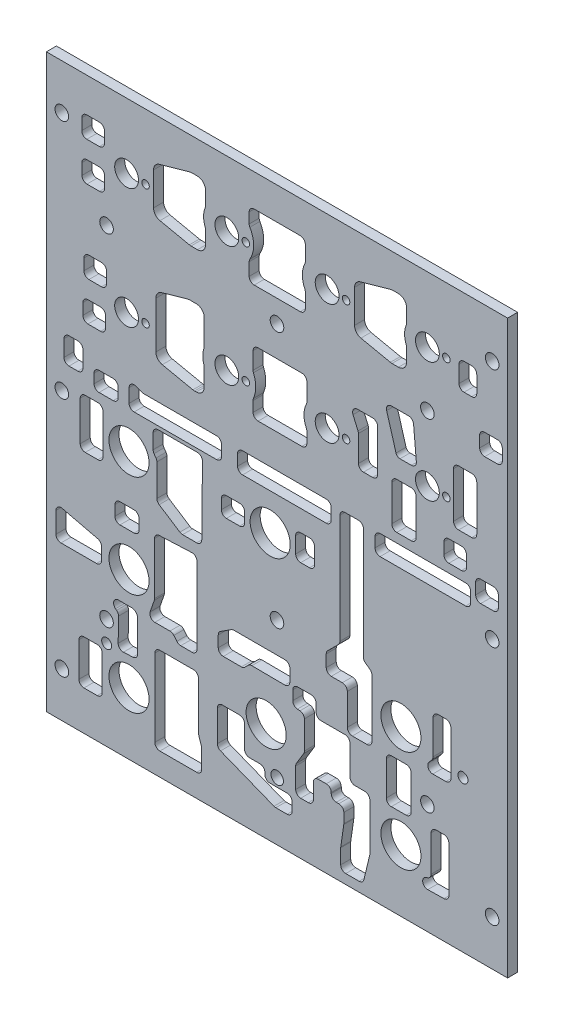
SolidWorks part; units mm, degrees
ref_plane "Front Plane" through (0, 0, 0) normal (0, 0, 1) x (1, 0, 0)
ref_plane "Top Plane" through (0, 0, 0) normal (0, 1, 0) x (1, 0, 0)
ref_plane "Right Plane" through (0, 0, 0) normal (1, 0, 0) x (0, 0, -1)
sketch "Sketch1" plane through (0, 0, 0) normal (0, 0, 1) x (1, 0, 0)
  line L4 (0, 180.975) -> (-146.05, 180.975)
  line L5 (-146.05, 180.975) -> (-146.05, 0)
  line L6 (-146.05, 0) -> (0, 0)
  line L7 (0, 0) -> (0, 180.975)
  line L8 (0, 180.975) -> (-146.05, 180.975)
  line L9 (-146.05, 180.975) -> (-146.05, 0)
  line L10 (-146.05, 0) -> (0, 0)
  line L11 (0, 0) -> (0, 180.975)
  dimension "D1" = 0
extrude "Boss-Extrude1" add sketch "Sketch1" against normal blind 3.175
hole_wizard "#6 Clearance Hole1" positions "Sketch3" profile "Sketch2" hole size "#6" standard "ANSI Inch" end condition through all
sketch "Sketch3" plane through (0, 0, -3.175) normal (0, 0, -1) x (-1, 0, 0)
  point P0 (25.4, 142.875)
  point P7 (73.025, 142.875)
  point P10 (127, 142.875)
  point P13 (25.4, 34.925)
  point P16 (73.025, 61.647)
  point P19 (127, 34.925)
  point P22 (4.8895, 14.2875)
  point P25 (141.1605, 14.2875)
  point P28 (4.8895, 90.4875)
  point P31 (141.1605, 90.4875)
  point P34 (141.1605, 166.6875)
  point P37 (4.8895, 166.6875)
sketch "Sketch2" plane through (-25.4, 142.875, -3.175) normal (1, 0, 0) x (0, 1, 0)
  line L0 (0, 0) -> (0, 3.175)
  line L1 (0, 3.175) -> (2.1526, 3.175)
  line L2 (2.1526, 3.175) -> (2.1526, 0)
  line L5 (2.1526, 0) -> (0, 0)
  line L11 (0, -6.35) -> (0, 107.95) construction
  dimension "Thru Hole Dia." = 4.3053
  dimension "Thru Hole Depth" = 3.175
hole_wizard "19/64 (0.29688) Diameter Hole1" positions "Sketch5" profile "Sketch4" hole size "19/64" standard "ANSI Inch" end condition through all
sketch "Sketch5" plane through (0, 0, -3.175) normal (0, 0, -1) x (-1, 0, 0)
  point P0 (25.4, 160.3248)
  point P3 (57.15, 160.3248)
  point P6 (88.9, 160.3248)
  point P9 (120.65, 160.3248)
  point P12 (25.4, 122.2248)
  point P15 (57.15, 122.2248)
  point P18 (88.9, 122.2248)
  point P21 (120.65, 122.2248)
sketch "Sketch4" plane through (-25.4, 160.3248, -3.175) normal (1, 0, 0) x (0, 1, 0)
  line L0 (0, 0) -> (0, 3.175)
  line L1 (0, 3.175) -> (3.7704, 3.175)
  line L2 (3.7704, 3.175) -> (3.7704, 0)
  line L5 (3.7704, 0) -> (0, 0)
  line L11 (0, -6.35) -> (0, 107.95) construction
  dimension "Thru Hole Dia." = 7.5408
  dimension "Thru Hole Depth" = 3.175
hole_wizard "1/2 (0.5) Diameter Hole1" positions "Sketch7" profile "Sketch6" hole size "1/2" standard "ANSI Inch" end condition through all
sketch "Sketch7" plane through (0, 0, -3.175) normal (0, 0, -1) x (-1, 0, 0)
  point P0 (75.184, 84.455)
  point P3 (119.888, 84.455)
  point P6 (119.888, 52.07)
  point P9 (33.782, 52.07)
  point P12 (33.782, 19.685)
  point P15 (119.888, 19.685)
  point P18 (76.454, 31.496)
sketch "Sketch6" plane through (-75.184, 84.455, -3.175) normal (1, 0, 0) x (0, 1, 0)
  line L0 (0, 0) -> (0, 3.175)
  line L1 (0, 3.175) -> (6.35, 3.175)
  line L2 (6.35, 3.175) -> (6.35, 0)
  line L5 (6.35, 0) -> (0, 0)
  line L11 (0, -6.35) -> (0, 107.95) construction
  dimension "Thru Hole Dia." = 12.7
  dimension "Thru Hole Depth" = 3.175
hole_wizard "5/32 (0.15625) Diameter Hole1" positions "Sketch9" profile "Sketch8" hole size "5/32" standard "ANSI Inch" end condition through all
sketch "Sketch9" plane through (0, 0, -3.175) normal (0, 0, -1) x (-1, 0, 0)
  point P0 (72.9632, 18.4682)
sketch "Sketch8" plane through (-72.9632, 18.4682, -3.175) normal (1, 0, 0) x (0, 1, 0)
  line L0 (0, 0) -> (0, 3.175)
  line L1 (0, 3.175) -> (1.9844, 3.175)
  line L2 (1.9844, 3.175) -> (1.9844, 0)
  line L5 (1.9844, 0) -> (0, 0)
  line L11 (0, -6.35) -> (0, 107.95) construction
  dimension "Thru Hole Dia." = 3.9688
  dimension "Thru Hole Depth" = 3.175
hole_wizard "3/32 (0.09375) Diameter Hole1" positions "Sketch10" profile "Sketch11" hole size "3/32" standard "ANSI Inch" end condition through all
sketch "Sketch10" plane through (0, 0, -3.175) normal (0, 0, -1) x (-1, 0, 0)
  point P0 (19.4, 160.3248)
  point P2 (51.15, 160.3248)
  point P4 (82.9, 160.3248)
  point P6 (114.65, 160.3248)
  point P8 (114.65, 122.2248)
  point P10 (82.9, 122.2248)
  point P12 (51.15, 122.2248)
  point P14 (19.4, 122.2248)
sketch "Sketch11" plane through (-19.4, 160.3248, -3.175) normal (1, 0, 0) x (0, 1, 0)
  line L0 (0, 0) -> (0, 3.175)
  line L1 (0, 3.175) -> (1.1906, 3.175)
  line L2 (1.1906, 3.175) -> (1.1906, 0)
  line L5 (1.1906, 0) -> (0, 0)
  line L11 (0, -6.35) -> (0, 107.95) construction
  dimension "Thru Hole Dia." = 2.3812
  dimension "Thru Hole Depth" = 3.175
sketch "Sketch14" plane through (0, 0, -3.175) normal (0, 0, -1) x (-1, 0, 0)
  line L0 (9.7672, 160.6329) -> (9.7672, 155.3272)
  line L1 (11.3547, 153.7397) -> (13.8015, 153.7397)
  line L2 (15.389, 155.3272) -> (15.389, 160.6329)
  line L3 (13.8015, 162.2204) -> (11.3547, 162.2204)
  line L4 (34.5586, 170.4142) -> (36.4003, 170.4142)
  line L5 (37.0961, 170.317) -> (46.6191, 167.6046)
  line L6 (48.4633, 165.1617) -> (48.4633, 154.7406)
  line L7 (46.4489, 152.2556) -> (37.1235, 150.2836)
  line L8 (36.598, 150.2286) -> (34.5586, 150.2286)
  line L9 (32.0186, 152.7686) -> (32.0186, 156.9396)
  line L10 (32.0186, 163.6743) -> (32.0186, 167.8742)
  line L11 (98.2115, 170.808) -> (100.0532, 170.808)
  line L12 (100.749, 170.7109) -> (110.272, 167.9984)
  line L13 (112.1162, 165.5556) -> (112.1162, 155.1345)
  line L14 (110.1017, 152.6494) -> (100.7763, 150.6774)
  line L15 (100.2508, 150.6225) -> (98.2115, 150.6225)
  line L16 (95.6715, 153.1625) -> (95.6715, 157.3335)
  line L17 (95.6715, 164.0681) -> (95.6715, 168.268)
  line L18 (81.8281, 169.1678) -> (81.8281, 165.8804)
  line L19 (80.2406, 149.9091) -> (65.6522, 149.9091)
  line L20 (64.0647, 151.4966) -> (64.0647, 156.2088)
  line L21 (65.6522, 170.7553) -> (80.2406, 170.7553)
  line L22 (81.8281, 155.5212) -> (81.8281, 151.4966)
  line L23 (64.0647, 164.4051) -> (64.0647, 169.1678)
  line L24 (129.2512, 170.0673) -> (133.2539, 170.0673)
  line L25 (134.8414, 168.4798) -> (134.8414, 164.9772)
  line L26 (133.2539, 163.3897) -> (129.2512, 163.3897)
  line L27 (127.6637, 164.9772) -> (127.6637, 168.4798)
  line L28 (129.2048, 157.7974) -> (133.2075, 157.7974)
  line L29 (134.795, 156.2099) -> (134.795, 152.7072)
  line L30 (133.2075, 151.1197) -> (129.2048, 151.1197)
  line L31 (127.6173, 152.7072) -> (127.6173, 156.2099)
  line L38 (9.7672, 131.1028) -> (9.7672, 116.698)
  line L39 (3.2616, 146.0268) -> (7.2643, 146.0268)
  line L40 (8.8518, 144.4393) -> (8.8518, 140.9366)
  line L41 (7.2643, 139.3491) -> (3.2616, 139.3491)
  line L42 (1.6741, 140.9366) -> (1.6741, 144.4393)
  line L43 (31.3598, 138.4891) -> (36.773, 138.4891)
  line L44 (38.2969, 136.4568) -> (35.3321, 126.2979)
  line L45 (34.083, 125.3612) -> (30.4776, 125.3612)
  line L46 (28.8963, 127.0889) -> (29.7785, 137.0417)
  line L47 (11.3547, 115.1105) -> (15.5328, 115.1105)
  line L48 (17.1203, 116.698) -> (17.1203, 131.1028)
  line L49 (15.5328, 132.6903) -> (11.3547, 132.6903)
  line L50 (48.956, 130.0101) -> (47.363, 126.3421)
  line L51 (47.2316, 125.7097) -> (47.2316, 117.4914)
  line L52 (45.6441, 115.9039) -> (42.7293, 115.9039)
  line L53 (41.1418, 117.4914) -> (41.1418, 130.6425)
  line L54 (42.7293, 132.23) -> (47.4999, 132.23)
  line L55 (80.6037, 131.7198) -> (80.6037, 126.3538)
  line L56 (79.0162, 113.2168) -> (65.1559, 113.2168)
  line L57 (63.5684, 114.8043) -> (63.5684, 118.2429)
  line L58 (65.1559, 133.3073) -> (79.0162, 133.3073)
  line L59 (80.6037, 118.0601) -> (80.6037, 114.8043)
  line L60 (63.5684, 126.171) -> (63.5684, 131.7198)
  line L61 (98.5982, 135.6202) -> (100.6455, 135.6202)
  line L62 (101.3413, 135.523) -> (109.5302, 133.1906)
  line L63 (111.3744, 130.7477) -> (111.3744, 116.0074)
  line L64 (109.3599, 113.5224) -> (99.6649, 111.4722)
  line L65 (99.1394, 111.4172) -> (98.5982, 111.4172)
  line L66 (96.0582, 113.9572) -> (96.0582, 119.3928)
  line L67 (96.0582, 125.1954) -> (96.0582, 133.0802)
  line L68 (128.5836, 131.9356) -> (132.5863, 131.9356)
  line L69 (134.1738, 130.3481) -> (134.1738, 126.8454)
  line L70 (132.5863, 125.2579) -> (128.5836, 125.2579)
  line L71 (126.9961, 126.8454) -> (126.9961, 130.3481)
  line L72 (128.8955, 119.5754) -> (132.8982, 119.5754)
  line L73 (134.4857, 117.9879) -> (134.4857, 114.4852)
  line L74 (132.8982, 112.8977) -> (128.8955, 112.8977)
  line L75 (127.308, 114.4852) -> (127.308, 117.9879)
  line L80 (134.4857, 99.9647) -> (134.4857, 105.0965)
  line L81 (136.0732, 106.684) -> (138.8818, 106.684)
  line L82 (140.4693, 105.0965) -> (140.4693, 99.9647)
  line L83 (138.8818, 98.3772) -> (136.0732, 98.3772)
  line L84 (4.5173, 105.1016) -> (8.52, 105.1016)
  line L85 (10.1075, 103.5141) -> (10.1075, 100.0114)
  line L86 (8.52, 98.4239) -> (4.5173, 98.4239)
  line L87 (2.9298, 100.0114) -> (2.9298, 103.5141)
  line L88 (14.5909, 111.1372) -> (18.5937, 111.1372)
  line L89 (20.1812, 109.5497) -> (20.1812, 106.0471)
  line L90 (18.5937, 104.4596) -> (14.5909, 104.4596)
  line L91 (13.0034, 106.0471) -> (13.0034, 109.5497)
  line L92 (30.5353, 119.2048) -> (35.0928, 119.2048)
  line L93 (36.6803, 117.6173) -> (36.6803, 106.232)
  line L94 (35.0928, 104.6445) -> (30.5353, 104.6445)
  line L95 (28.9478, 106.232) -> (28.9478, 117.6173)
  line L96 (45.6441, 65.1535) -> (45.6441, 100.3349)
  line L97 (47.2316, 101.9224) -> (51.5303, 101.9224)
  line L98 (53.1178, 100.3349) -> (53.1178, 65.7835)
  line L100 (42.9626, 43.3689) -> (42.9626, 61.5953)
  line L101 (43.6218, 62.8831) -> (44.9849, 63.8657)
  line L102 (53.5828, 64.661) -> (56.969, 61.2747)
  line L103 (57.434, 60.1522) -> (57.434, 56.3979)
  line L104 (55.8465, 54.8104) -> (52.3434, 54.8104)
  line L105 (50.7559, 53.2229) -> (50.7559, 43.3689)
  line L106 (49.1684, 41.7814) -> (44.5501, 41.7814)
  line L107 (67.1117, 82.7287) -> (67.1117, 87.7639)
  line L108 (65.5242, 89.3514) -> (62.7089, 89.3514)
  line L109 (61.1214, 87.7639) -> (61.1214, 82.7287)
  line L110 (62.7089, 81.1412) -> (65.5242, 81.1412)
  line L111 (17.9628, 45.6888) -> (17.9628, 59.6872)
  line L112 (19.5503, 61.2747) -> (21.9934, 61.2747)
  line L113 (23.5809, 59.6872) -> (23.5809, 48.8911)
  line L114 (23.9452, 47.8792) -> (24.9202, 46.7007)
  line L115 (23.697, 44.1013) -> (19.5503, 44.1013)
  line L116 (25.4886, 14.7678) -> (25.6589, 14.7487)
  line L117 (24.2487, 16.3262) -> (24.2487, 27.6802)
  line L118 (22.6612, 29.2677) -> (20.1812, 29.2677)
  line L119 (18.5937, 27.6802) -> (18.5937, 13.2755)
  line L120 (20.1548, 11.6882) -> (25.2848, 11.603)
  line L121 (32.1228, 42.5427) -> (36.8165, 42.5427)
  line L122 (38.404, 40.9552) -> (38.404, 30.1729)
  line L123 (36.8165, 28.5854) -> (32.1228, 28.5854)
  line L124 (30.5353, 30.1729) -> (30.5353, 40.9552)
  line L131 (43.6218, 25.2523) -> (43.6218, 12.2392)
  line L132 (43.6651, 11.8711) -> (43.6953, 11.7446)
  line L133 (43.6953, 11.7446) -> (45.484, 4.241)
  line L134 (47.0282, 3.0216) -> (51.2631, 3.0216)
  line L135 (52.8506, 4.6091) -> (52.8506, 9.2853)
  line L136 (52.8343, 9.5123) -> (51.8747, 16.1533)
  line L137 (51.8584, 16.3803) -> (51.8584, 19.4808)
  line L138 (53.4459, 21.0683) -> (54.259, 21.0683)
  line L139 (55.8465, 22.6558) -> (55.8465, 22.9529)
  line L140 (57.434, 24.5404) -> (59.9239, 24.5404)
  line L142 (65.7683, 40.3849) -> (66.5835, 40.4562)
  line L143 (68.0326, 42.0377) -> (68.0326, 44.998)
  line L144 (66.4451, 46.5855) -> (62.2379, 46.5855)
  line L145 (60.6504, 44.998) -> (60.6504, 42.5992)
  line L146 (59.0629, 41.0117) -> (51.4951, 41.0117)
  line L147 (49.9076, 39.4242) -> (49.9076, 30.1729)
  line L148 (48.3201, 28.5854) -> (45.2093, 28.5854)
  line L149 (43.6218, 26.9979) -> (43.6218, 25.2523)
  line L150 (68.9553, 46.6546) -> (68.9553, 50.4494)
  line L151 (70.5428, 52.0369) -> (86.6326, 52.0369)
  line L152 (87.4873, 51.7871) -> (90.8944, 49.6101)
  line L153 (91.6271, 48.2724) -> (91.6271, 44.761)
  line L154 (90.0396, 43.1735) -> (84.3014, 43.1735)
  line L155 (83.1789, 43.6384) -> (82.1297, 44.6876)
  line L156 (80.9942, 45.1525) -> (70.5558, 45.0672)
  line L157 (67.1117, 24.5868) -> (67.1117, 18.1303)
  line L158 (65.5242, 16.5428) -> (63.0989, 16.5428)
  line L163 (61.5114, 18.1303) -> (61.5114, 22.9529)
  line L165 (66.8832, 25.4074) -> (64.5524, 29.2677)
  line L166 (64.3238, 30.0883) -> (64.3238, 38.9242)
  line L167 (91.9128, 18.299) -> (91.9128, 28.1134)
  line L168 (90.3253, 29.7009) -> (84.8895, 29.7009)
  line L169 (83.302, 28.1134) -> (83.302, 21.1236)
  line L170 (81.7145, 19.5361) -> (78.4438, 19.5361)
  line L171 (76.8563, 17.9486) -> (76.8563, 17.3807)
  line L172 (75.2688, 15.7932) -> (69.8184, 15.7932)
  line L173 (68.2309, 14.2057) -> (68.2309, 11.594)
  line L174 (69.8184, 10.0065) -> (73.3881, 10.0065)
  line L175 (73.9724, 10.1179) -> (90.9097, 16.8229)
  line L176 (84.8489, 87.7639) -> (89.0654, 87.7639)
  line L177 (90.6529, 86.1764) -> (90.6529, 83.1046)
  line L178 (89.0654, 81.5171) -> (84.8489, 81.5171)
  line L179 (83.2614, 83.1046) -> (83.2614, 86.1764)
  line L180 (129.7198, 92.9203) -> (133.7466, 92.9203)
  line L181 (135.3341, 91.3328) -> (135.3341, 78.857)
  line L182 (133.7466, 77.2695) -> (129.7198, 77.2695)
  line L183 (128.1323, 78.857) -> (128.1323, 91.3328)
  line L184 (143.02, 56.7173) -> (143.02, 50.184)
  line L185 (141.4325, 48.5965) -> (130.1711, 48.5965)
  line L186 (128.5836, 50.184) -> (128.5836, 54.036)
  line L187 (129.8034, 55.5803) -> (141.0648, 58.2616)
  line L188 (135.7336, 24.8954) -> (135.7336, 14.0589)
  line L189 (134.1461, 12.4714) -> (129.9507, 12.4714)
  line L190 (128.3632, 14.0589) -> (128.3632, 24.8954)
  line L191 (129.9507, 26.4829) -> (134.1461, 26.4829)
  line L192 (98.4374, 70.1232) -> (102.927, 70.1232)
  line L193 (103.7933, 70.3805) -> (110.3296, 74.6375)
  line L194 (111.0507, 75.9677) -> (111.0507, 86.0205)
  line L195 (111.3413, 86.936) -> (111.9636, 87.8177)
  line L196 (112.2542, 88.7332) -> (112.2542, 93.4348)
  line L197 (110.6667, 95.0223) -> (98.2147, 95.0223)
  line L198 (96.6273, 93.4186) -> (96.85, 71.6944)
  line L199 (13.2867, 101.7189) -> (40.3927, 101.7189)
  line L200 (41.9802, 100.1314) -> (41.9802, 96.9635)
  line L201 (40.3927, 95.376) -> (13.2867, 95.376)
  line L202 (11.6992, 96.9635) -> (11.6992, 100.1314)
  line L203 (83.9216, 102.6251) -> (57.434, 102.6251)
  line L204 (55.8465, 101.0376) -> (55.8465, 97.6017)
  line L205 (57.434, 96.0142) -> (83.9216, 96.0142)
  line L206 (85.5091, 97.6017) -> (85.5091, 101.0376)
  line L207 (92.1689, 102.6251) -> (115.232, 102.6251)
  line L208 (115.789, 102.726) -> (117.7111, 103.4462)
  line L209 (119.8556, 101.9596) -> (119.8556, 97.6777)
  line L210 (118.2681, 96.0902) -> (92.1689, 96.0902)
  line L211 (90.5814, 97.6777) -> (90.5814, 101.0376)
  line L212 (124.9027, 101.9596) -> (129.3791, 101.9596)
  line L213 (130.9666, 100.3721) -> (130.9666, 97.4731)
  line L214 (129.3791, 95.8856) -> (124.9027, 95.8856)
  line L215 (123.3152, 97.4731) -> (123.3152, 100.3721)
  line L216 (118.2868, 62.8831) -> (122.7428, 62.8831)
  line L217 (124.3303, 64.4706) -> (124.3303, 67.6675)
  line L218 (122.7428, 69.255) -> (118.2868, 69.255)
  line L219 (116.6993, 67.6675) -> (116.6993, 64.4706)
  line L220 (99.9975, 66.6672) -> (110.2768, 66.2149)
  line L221 (111.7946, 64.6289) -> (111.7946, 48.1514)
  line L222 (111.8816, 47.6331) -> (113.2086, 43.7913)
  line L223 (111.7081, 41.6855) -> (106.9185, 41.6855)
  line L224 (105.6937, 41.108) -> (104.7376, 39.9485)
  line L225 (103.5128, 39.371) -> (99.9277, 39.371)
  line L226 (98.3402, 40.9585) -> (98.3402, 65.0812)
  line L227 (123.3155, 30.1394) -> (123.1999, 37.6519)
  line L231 (117.1597, 40.098) -> (117.1597, 30.2424)
  line L232 (118.6794, 28.6564) -> (121.6604, 28.5289)
  line L235 (119.0974, 42.0356) -> (123.1757, 42.0356)
  line L236 (124.1569, 39.2002) -> (123.806, 38.9242)
  line L238 (99.477, 34.8237) -> (110.1206, 34.8237)
  line L239 (111.7081, 33.2362) -> (111.7081, 8.7739)
  line L240 (110.1206, 7.1864) -> (98.4375, 7.1864)
  line L241 (96.85, 8.7739) -> (96.85, 14.4973)
  line L242 (96.9277, 14.9877) -> (97.8118, 17.7095)
  line L243 (97.8895, 18.1999) -> (97.8895, 33.2362)
  arc A0 (13.8015, 153.7397) -> (15.389, 155.3272) centre (13.8015, 155.3272) ccw
  arc A1 (9.7672, 160.6329) -> (11.3547, 162.2204) centre (11.3547, 160.6329) cw
  arc A2 (15.389, 160.6329) -> (13.8015, 162.2204) centre (13.8015, 160.6329) ccw
  arc A3 (9.7672, 155.3272) -> (11.3547, 153.7397) centre (11.3547, 155.3272) ccw
  arc A4 (34.5586, 150.2286) -> (32.0186, 152.7686) centre (34.5586, 152.7686) cw
  arc A5 (37.1235, 150.2836) -> (36.598, 150.2286) centre (36.598, 152.7686) cw
  arc A6 (48.4633, 154.7406) -> (46.4489, 152.2556) centre (45.9233, 154.7406) cw
  arc A7 (46.6191, 167.6046) -> (48.4633, 165.1617) centre (45.9233, 165.1617) cw
  arc A8 (36.4003, 170.4142) -> (37.0961, 170.317) centre (36.4003, 167.8742) cw
  arc A9 (34.5586, 170.4142) -> (32.0186, 167.8742) centre (34.5586, 167.8742) ccw
  arc A10 (32.1741, 157.8147) -> (32.1741, 162.7992) centre (25.3826, 160.3069) ccw
  arc A11 (32.1741, 162.7992) -> (32.0186, 163.6743) centre (34.5586, 163.6743) cw
  arc A12 (32.1741, 157.8147) -> (32.0186, 156.9396) centre (34.5586, 156.9396) ccw
  arc A13 (98.2115, 150.6225) -> (95.6715, 153.1625) centre (98.2115, 153.1625) cw
  arc A14 (100.7763, 150.6774) -> (100.2508, 150.6225) centre (100.2508, 153.1625) cw
  arc A15 (112.1162, 155.1345) -> (110.1017, 152.6494) centre (109.5762, 155.1345) cw
  arc A16 (110.272, 167.9984) -> (112.1162, 165.5556) centre (109.5762, 165.5556) cw
  arc A17 (100.0532, 170.808) -> (100.749, 170.7109) centre (100.0532, 168.268) cw
  arc A18 (98.2115, 170.808) -> (95.6715, 168.268) centre (98.2115, 168.268) ccw
  arc A19 (95.8269, 158.2085) -> (95.8269, 163.1931) centre (89.0355, 160.7008) ccw
  arc A20 (95.8269, 163.1931) -> (95.6715, 164.0681) centre (98.2115, 164.0681) cw
  arc A21 (95.8269, 158.2085) -> (95.6715, 157.3335) centre (98.2115, 157.3335) ccw
  arc A22 (64.2216, 156.8969) -> (64.2216, 163.7169) centre (57.1326, 160.3069) ccw
  arc A23 (81.6085, 165.0748) -> (81.6085, 156.3268) centre (89.0355, 160.7008) ccw
  arc A24 (64.2216, 163.7169) -> (64.0647, 164.4051) centre (65.6522, 164.4051) cw
  arc A25 (64.2216, 156.8969) -> (64.0647, 156.2088) centre (65.6522, 156.2088) ccw
  arc A26 (81.6085, 156.3268) -> (81.8281, 155.5212) centre (80.2406, 155.5212) cw
  arc A27 (81.6085, 165.0748) -> (81.8281, 165.8804) centre (80.2406, 165.8804) ccw
  arc A28 (81.8281, 169.1678) -> (80.2406, 170.7553) centre (80.2406, 169.1678) ccw
  arc A29 (64.0647, 169.1678) -> (65.6522, 170.7553) centre (65.6522, 169.1678) cw
  arc A30 (65.6522, 149.9091) -> (64.0647, 151.4966) centre (65.6522, 151.4966) cw
  arc A31 (81.8281, 151.4966) -> (80.2406, 149.9091) centre (80.2406, 151.4966) cw
  arc A32 (129.2512, 170.0673) -> (127.6637, 168.4798) centre (129.2512, 168.4798) ccw
  arc A33 (129.2512, 163.3897) -> (127.6637, 164.9772) centre (129.2512, 164.9772) cw
  arc A34 (134.8414, 164.9772) -> (133.2539, 163.3897) centre (133.2539, 164.9772) cw
  arc A35 (133.2539, 170.0673) -> (134.8414, 168.4798) centre (133.2539, 168.4798) cw
  arc A36 (129.2048, 157.7974) -> (127.6173, 156.2099) centre (129.2048, 156.2099) ccw
  arc A37 (129.2048, 151.1197) -> (127.6173, 152.7072) centre (129.2048, 152.7072) cw
  arc A38 (134.795, 152.7072) -> (133.2075, 151.1197) centre (133.2075, 152.7072) cw
  arc A39 (133.2075, 157.7974) -> (134.795, 156.2099) centre (133.2075, 156.2099) cw
  arc A50 (29.7785, 137.0417) -> (31.3598, 138.4891) centre (31.3598, 136.9016) cw
  arc A51 (3.2616, 146.0268) -> (1.6741, 144.4393) centre (3.2616, 144.4393) ccw
  arc A52 (3.2616, 139.3491) -> (1.6741, 140.9366) centre (3.2616, 140.9366) cw
  arc A53 (8.8518, 140.9366) -> (7.2643, 139.3491) centre (7.2643, 140.9366) cw
  arc A54 (7.2643, 146.0268) -> (8.8518, 144.4393) centre (7.2643, 144.4393) cw
  arc A55 (128.5836, 131.9356) -> (126.9961, 130.3481) centre (128.5836, 130.3481) ccw
  arc A56 (36.773, 138.4891) -> (38.2969, 136.4568) centre (36.773, 136.9016) cw
  arc A57 (30.4776, 125.3612) -> (28.8963, 127.0889) centre (30.4776, 126.9487) cw
  arc A58 (35.3321, 126.2979) -> (34.083, 125.3612) centre (34.083, 126.6624) cw
  arc A60 (9.7672, 116.698) -> (11.3547, 115.1105) centre (11.3547, 116.698) ccw
  arc A61 (15.5328, 115.1105) -> (17.1203, 116.698) centre (15.5328, 116.698) ccw
  arc A62 (17.1203, 131.1028) -> (15.5328, 132.6903) centre (15.5328, 131.1028) ccw
  arc A63 (9.7672, 131.1028) -> (11.3547, 132.6903) centre (11.3547, 131.1028) cw
  arc A64 (42.7293, 115.9039) -> (41.1418, 117.4914) centre (42.7293, 117.4914) cw
  arc A65 (47.2316, 117.4914) -> (45.6441, 115.9039) centre (45.6441, 117.4914) cw
  arc A66 (47.363, 126.3421) -> (47.2316, 125.7097) centre (48.8191, 125.7097) ccw
  arc A67 (41.1418, 130.6425) -> (42.7293, 132.23) centre (42.7293, 130.6425) cw
  arc A68 (48.956, 130.0101) -> (47.4999, 132.23) centre (47.4999, 130.6425) ccw
  arc A69 (80.4797, 125.7387) -> (80.4797, 118.6752) centre (88.8826, 122.2069) ccw
  arc A70 (63.7326, 118.9461) -> (63.7326, 125.4678) centre (57.1326, 122.2069) ccw
  arc A71 (63.7326, 125.4678) -> (63.5684, 126.171) centre (65.1559, 126.171) cw
  arc A72 (63.7326, 118.9461) -> (63.5684, 118.2429) centre (65.1559, 118.2429) ccw
  arc A73 (65.1559, 113.2168) -> (63.5684, 114.8043) centre (65.1559, 114.8043) cw
  arc A74 (80.6037, 114.8043) -> (79.0162, 113.2168) centre (79.0162, 114.8043) cw
  arc A75 (80.4797, 118.6752) -> (80.6037, 118.0601) centre (79.0162, 118.0601) cw
  arc A76 (80.4797, 125.7387) -> (80.6037, 126.3538) centre (79.0162, 126.3538) ccw
  arc A77 (80.6037, 131.7198) -> (79.0162, 133.3073) centre (79.0162, 131.7198) ccw
  arc A78 (63.5684, 131.7198) -> (65.1559, 133.3073) centre (65.1559, 131.7198) cw
  arc A79 (98.5982, 111.4172) -> (96.0582, 113.9572) centre (98.5982, 113.9572) cw
  arc A80 (99.6649, 111.4722) -> (99.1394, 111.4172) centre (99.1394, 113.9572) cw
  arc A81 (111.3744, 116.0074) -> (109.3599, 113.5224) centre (108.8344, 116.0074) cw
  arc A82 (109.5302, 133.1906) -> (111.3744, 130.7477) centre (108.8344, 130.7477) cw
  arc A83 (100.6455, 135.6202) -> (101.3413, 135.523) centre (100.6455, 133.0802) cw
  arc A84 (98.5982, 135.6202) -> (96.0582, 133.0802) centre (98.5982, 133.0802) ccw
  arc A85 (96.1501, 119.9657) -> (96.1501, 124.6224) centre (89.0819, 122.2941) ccw
  arc A86 (96.1501, 124.6224) -> (96.0582, 125.1954) centre (97.8895, 125.1954) cw
  arc A87 (96.1501, 119.9657) -> (96.0582, 119.3928) centre (97.8895, 119.3928) ccw
  arc A88 (128.5836, 125.2579) -> (126.9961, 126.8454) centre (128.5836, 126.8454) cw
  arc A89 (134.1738, 126.8454) -> (132.5863, 125.2579) centre (132.5863, 126.8454) cw
  arc A90 (132.5863, 131.9356) -> (134.1738, 130.3481) centre (132.5863, 130.3481) cw
  arc A91 (128.8955, 119.5754) -> (127.308, 117.9879) centre (128.8955, 117.9879) ccw
  arc A92 (128.8955, 112.8977) -> (127.308, 114.4852) centre (128.8955, 114.4852) cw
  arc A93 (134.4857, 114.4852) -> (132.8982, 112.8977) centre (132.8982, 114.4852) cw
  arc A94 (132.8982, 119.5754) -> (134.4857, 117.9879) centre (132.8982, 117.9879) cw
  arc A99 (134.4857, 99.9647) -> (136.0732, 98.3772) centre (136.0732, 99.9647) ccw
  arc A100 (140.4693, 99.9647) -> (138.8818, 98.3772) centre (138.8818, 99.9647) cw
  arc A101 (138.8818, 106.684) -> (140.4693, 105.0965) centre (138.8818, 105.0965) cw
  arc A102 (134.4857, 105.0965) -> (136.0732, 106.684) centre (136.0732, 105.0965) cw
  arc A103 (4.5173, 105.1016) -> (2.9298, 103.5141) centre (4.5173, 103.5141) ccw
  arc A104 (4.5173, 98.4239) -> (2.9298, 100.0114) centre (4.5173, 100.0114) cw
  arc A105 (10.1075, 100.0114) -> (8.52, 98.4239) centre (8.52, 100.0114) cw
  arc A106 (8.52, 105.1016) -> (10.1075, 103.5141) centre (8.52, 103.5141) cw
  arc A107 (14.5909, 111.1372) -> (13.0034, 109.5497) centre (14.5909, 109.5497) ccw
  arc A108 (14.5909, 104.4596) -> (13.0034, 106.0471) centre (14.5909, 106.0471) cw
  arc A109 (20.1812, 106.0471) -> (18.5937, 104.4596) centre (18.5937, 106.0471) cw
  arc A110 (18.5937, 111.1372) -> (20.1812, 109.5497) centre (18.5937, 109.5497) cw
  arc A111 (30.5353, 119.2048) -> (28.9478, 117.6173) centre (30.5353, 117.6173) ccw
  arc A112 (30.5353, 104.6445) -> (28.9478, 106.232) centre (30.5353, 106.232) cw
  arc A113 (36.6803, 106.232) -> (35.0928, 104.6445) centre (35.0928, 106.232) cw
  arc A114 (35.0928, 119.2048) -> (36.6803, 117.6173) centre (35.0928, 117.6173) cw
  arc A115 (45.6441, 100.3349) -> (47.2316, 101.9224) centre (47.2316, 100.3349) cw
  arc A116 (51.5303, 101.9224) -> (53.1178, 100.3349) centre (51.5303, 100.3349) cw
  arc A119 (53.1178, 65.7835) -> (53.5828, 64.661) centre (54.7053, 65.7835) ccw
  arc A120 (56.969, 61.2747) -> (57.434, 60.1522) centre (55.8465, 60.1522) cw
  arc A121 (57.434, 56.3979) -> (55.8465, 54.8104) centre (55.8465, 56.3979) cw
  arc A122 (42.9626, 43.3689) -> (44.5501, 41.7814) centre (44.5501, 43.3689) ccw
  arc A123 (50.7559, 43.3689) -> (49.1684, 41.7814) centre (49.1684, 43.3689) cw
  arc A124 (52.3434, 54.8104) -> (50.7559, 53.2229) centre (52.3434, 53.2229) ccw
  arc A125 (42.9626, 61.5953) -> (43.6218, 62.8831) centre (44.5501, 61.5953) cw
  arc A126 (45.6441, 65.1535) -> (44.9849, 63.8657) centre (44.0566, 65.1535) cw
  arc A127 (61.1214, 82.7287) -> (62.7089, 81.1412) centre (62.7089, 82.7287) ccw
  arc A128 (62.7089, 89.3514) -> (61.1214, 87.7639) centre (62.7089, 87.7639) ccw
  arc A129 (67.1117, 87.7639) -> (65.5242, 89.3514) centre (65.5242, 87.7639) ccw
  arc A130 (67.1117, 82.7287) -> (65.5242, 81.1412) centre (65.5242, 82.7287) cw
  arc A131 (17.9628, 59.6872) -> (19.5503, 61.2747) centre (19.5503, 59.6872) cw
  arc A132 (21.9934, 61.2747) -> (23.5809, 59.6872) centre (21.9934, 59.6872) cw
  arc A133 (23.5809, 48.8911) -> (23.9452, 47.8792) centre (25.1684, 48.8911) ccw
  arc A134 (24.9202, 46.7007) -> (23.697, 44.1013) centre (23.697, 45.6888) cw
  arc A135 (17.9628, 45.6888) -> (19.5503, 44.1013) centre (19.5503, 45.6888) ccw
  circle A136 centre (14.1329, 47.8792) radius 1.5875
  arc A137 (20.1812, 29.2677) -> (18.5937, 27.6802) centre (20.1812, 27.6802) ccw
  arc A138 (24.2487, 27.6802) -> (22.6612, 29.2677) centre (22.6612, 27.6802) ccw
  arc A139 (18.5937, 13.2755) -> (20.1548, 11.6882) centre (20.1812, 13.2755) ccw
  arc A140 (25.4886, 14.7678) -> (25.2848, 11.603) centre (25.3112, 13.1902) cw
  arc A141 (25.6589, 14.7487) -> (24.2487, 16.3262) centre (25.8362, 16.3262) cw
  arc A142 (32.1228, 42.5427) -> (30.5353, 40.9552) centre (32.1228, 40.9552) ccw
  arc A143 (36.8165, 42.5427) -> (38.404, 40.9552) centre (36.8165, 40.9552) cw
  arc A144 (38.404, 30.1729) -> (36.8165, 28.5854) centre (36.8165, 30.1729) cw
  arc A145 (32.1228, 28.5854) -> (30.5353, 30.1729) centre (32.1228, 30.1729) cw
  arc A151 (43.6218, 12.2392) -> (43.6651, 11.8711) centre (45.2093, 12.2392) ccw
  arc A152 (45.2093, 28.5854) -> (43.6218, 26.9979) centre (45.2093, 26.9979) ccw
  arc A153 (49.9076, 30.1729) -> (48.3201, 28.5854) centre (48.3201, 30.1729) cw
  arc A154 (51.4951, 41.0117) -> (49.9076, 39.4242) centre (51.4951, 39.4242) ccw
  arc A155 (60.6504, 42.5992) -> (59.0629, 41.0117) centre (59.0629, 42.5992) cw
  arc A156 (62.2379, 46.5855) -> (60.6504, 44.998) centre (62.2379, 44.998) ccw
  arc A157 (68.0326, 44.998) -> (66.4451, 46.5855) centre (66.4451, 44.998) ccw
  arc A158 (66.5835, 40.4562) -> (68.0326, 42.0377) centre (66.4451, 42.0377) ccw
  arc A159 (64.3238, 38.9242) -> (65.7683, 40.3849) centre (65.9067, 38.8034) cw
  arc A161 (55.8465, 22.9529) -> (57.434, 24.5404) centre (57.434, 22.9529) cw
  arc A162 (51.8584, 19.4808) -> (53.4459, 21.0683) centre (53.4459, 19.4808) cw
  arc A163 (51.8747, 16.1533) -> (51.8584, 16.3803) centre (53.4459, 16.3803) cw
  arc A164 (52.8506, 9.2853) -> (52.8343, 9.5123) centre (51.2631, 9.2853) ccw
  arc A165 (51.2631, 3.0216) -> (52.8506, 4.6091) centre (51.2631, 4.6091) ccw
  arc A166 (45.484, 4.241) -> (47.0282, 3.0216) centre (47.0282, 4.6091) ccw
  arc A167 (54.259, 21.0683) -> (55.8465, 22.6558) centre (54.259, 22.6558) ccw
  arc A168 (82.1297, 44.6876) -> (80.9942, 45.1525) centre (81.0072, 43.5651) ccw
  arc A169 (84.3014, 43.1735) -> (83.1789, 43.6384) centre (84.3014, 44.761) cw
  arc A170 (91.6271, 44.761) -> (90.0396, 43.1735) centre (90.0396, 44.761) cw
  arc A171 (90.8944, 49.6101) -> (91.6271, 48.2724) centre (90.0396, 48.2724) cw
  arc A172 (86.6326, 52.0369) -> (87.4873, 51.7871) centre (86.6326, 50.4494) cw
  arc A173 (68.9553, 50.4494) -> (70.5428, 52.0369) centre (70.5428, 50.4494) cw
  arc A174 (68.9553, 46.6546) -> (70.5558, 45.0672) centre (70.5428, 46.6546) ccw
  arc A175 (67.1117, 18.1303) -> (65.5242, 16.5428) centre (65.5242, 18.1303) cw
  arc A176 (63.0989, 16.5428) -> (61.5114, 18.1303) centre (63.0989, 18.1303) cw
  arc A177 (61.5114, 22.9529) -> (59.9239, 24.5404) centre (59.9239, 22.9529) ccw
  arc A178 (67.1117, 24.5868) -> (66.8832, 25.4074) centre (65.5242, 24.5868) ccw
  arc A179 (64.5524, 29.2677) -> (64.3238, 30.0883) centre (65.9113, 30.0883) cw
  arc A180 (91.9128, 18.299) -> (90.9097, 16.8229) centre (90.3253, 18.299) cw
  arc A181 (91.9128, 28.1134) -> (90.3253, 29.7009) centre (90.3253, 28.1134) ccw
  arc A182 (84.8895, 29.7009) -> (83.302, 28.1134) centre (84.8895, 28.1134) ccw
  arc A183 (83.302, 21.1236) -> (81.7145, 19.5361) centre (81.7145, 21.1236) cw
  arc A184 (78.4438, 19.5361) -> (76.8563, 17.9486) centre (78.4438, 17.9486) ccw
  arc A185 (76.8563, 17.3807) -> (75.2688, 15.7932) centre (75.2688, 17.3807) cw
  arc A186 (69.8184, 15.7932) -> (68.2309, 14.2057) centre (69.8184, 14.2057) ccw
  arc A187 (68.2309, 11.594) -> (69.8184, 10.0065) centre (69.8184, 11.594) ccw
  arc A188 (73.3881, 10.0065) -> (73.9724, 10.1179) centre (73.3881, 11.594) ccw
  arc A189 (89.0654, 87.7639) -> (90.6529, 86.1764) centre (89.0654, 86.1764) cw
  arc A190 (90.6529, 83.1046) -> (89.0654, 81.5171) centre (89.0654, 83.1046) cw
  arc A191 (84.8489, 81.5171) -> (83.2614, 83.1046) centre (84.8489, 83.1046) cw
  arc A192 (84.8489, 87.7639) -> (83.2614, 86.1764) centre (84.8489, 86.1764) ccw
  arc A193 (129.7198, 77.2695) -> (128.1323, 78.857) centre (129.7198, 78.857) cw
  arc A194 (135.3341, 78.857) -> (133.7466, 77.2695) centre (133.7466, 78.857) cw
  arc A195 (133.7466, 92.9203) -> (135.3341, 91.3328) centre (133.7466, 91.3328) cw
  arc A196 (129.7198, 92.9203) -> (128.1323, 91.3328) centre (129.7198, 91.3328) ccw
  arc A197 (128.5836, 54.036) -> (129.8034, 55.5803) centre (130.1711, 54.036) cw
  arc A198 (130.1711, 48.5965) -> (128.5836, 50.184) centre (130.1711, 50.184) cw
  arc A199 (143.02, 50.184) -> (141.4325, 48.5965) centre (141.4325, 50.184) cw
  arc A200 (143.02, 56.7173) -> (141.0648, 58.2616) centre (141.4325, 56.7173) ccw
  arc A201 (129.9507, 12.4714) -> (128.3632, 14.0589) centre (129.9507, 14.0589) cw
  arc A202 (135.7336, 14.0589) -> (134.1461, 12.4714) centre (134.1461, 14.0589) cw
  arc A203 (128.3632, 24.8954) -> (129.9507, 26.4829) centre (129.9507, 24.8954) cw
  arc A204 (135.7336, 24.8954) -> (134.1461, 26.4829) centre (134.1461, 24.8954) ccw
  arc A205 (98.2147, 95.0223) -> (96.6273, 93.4186) centre (98.2147, 93.4348) ccw
  arc A206 (112.2542, 93.4348) -> (110.6667, 95.0223) centre (110.6667, 93.4348) ccw
  arc A207 (111.9636, 87.8177) -> (112.2542, 88.7332) centre (110.6667, 88.7332) ccw
  arc A208 (111.0507, 86.0205) -> (111.3413, 86.936) centre (112.6382, 86.0205) cw
  arc A209 (110.3296, 74.6375) -> (111.0507, 75.9677) centre (109.4632, 75.9677) ccw
  arc A210 (102.927, 70.1232) -> (103.7933, 70.3805) centre (102.927, 71.7107) ccw
  arc A211 (98.4374, 70.1232) -> (96.85, 71.6944) centre (98.4374, 71.7107) cw
  arc A212 (40.3927, 101.7189) -> (41.9802, 100.1314) centre (40.3927, 100.1314) cw
  arc A213 (41.9802, 96.9635) -> (40.3927, 95.376) centre (40.3927, 96.9635) cw
  arc A214 (13.2867, 95.376) -> (11.6992, 96.9635) centre (13.2867, 96.9635) cw
  arc A215 (13.2867, 101.7189) -> (11.6992, 100.1314) centre (13.2867, 100.1314) ccw
  arc A216 (83.9216, 102.6251) -> (85.5091, 101.0376) centre (83.9216, 101.0376) cw
  arc A217 (83.9216, 96.0142) -> (85.5091, 97.6017) centre (83.9216, 97.6017) ccw
  arc A218 (55.8465, 97.6017) -> (57.434, 96.0142) centre (57.434, 97.6017) ccw
  arc A219 (57.434, 102.6251) -> (55.8465, 101.0376) centre (57.434, 101.0376) ccw
  arc A220 (115.232, 102.6251) -> (115.789, 102.726) centre (115.232, 104.2126) ccw
  arc A221 (117.7111, 103.4462) -> (119.8556, 101.9596) centre (118.2681, 101.9596) cw
  arc A222 (119.8556, 97.6777) -> (118.2681, 96.0902) centre (118.2681, 97.6777) cw
  arc A223 (92.1689, 96.0902) -> (90.5814, 97.6777) centre (92.1689, 97.6777) cw
  arc A224 (92.1689, 102.6251) -> (90.5814, 101.0376) centre (92.1689, 101.0376) ccw
  arc A225 (129.3791, 101.9596) -> (130.9666, 100.3721) centre (129.3791, 100.3721) cw
  arc A226 (130.9666, 97.4731) -> (129.3791, 95.8856) centre (129.3791, 97.4731) cw
  arc A227 (124.9027, 95.8856) -> (123.3152, 97.4731) centre (124.9027, 97.4731) cw
  arc A228 (124.9027, 101.9596) -> (123.3152, 100.3721) centre (124.9027, 100.3721) ccw
  arc A229 (118.2868, 69.255) -> (116.6993, 67.6675) centre (118.2868, 67.6675) ccw
  arc A230 (118.2868, 62.8831) -> (116.6993, 64.4706) centre (118.2868, 64.4706) cw
  arc A231 (122.7428, 62.8831) -> (124.3303, 64.4706) centre (122.7428, 64.4706) ccw
  arc A232 (124.3303, 67.6675) -> (122.7428, 69.255) centre (122.7428, 67.6675) ccw
  arc A233 (99.9277, 39.371) -> (98.3402, 40.9585) centre (99.9277, 40.9585) cw
  arc A234 (104.7376, 39.9485) -> (103.5128, 39.371) centre (103.5128, 40.9585) cw
  arc A235 (106.9185, 41.6855) -> (105.6937, 41.108) centre (106.9185, 40.098) ccw
  arc A236 (113.2086, 43.7913) -> (111.7081, 41.6855) centre (111.7081, 43.273) cw
  arc A237 (111.7946, 48.1514) -> (111.8816, 47.6331) centre (113.3821, 48.1514) ccw
  arc A238 (110.2768, 66.2149) -> (111.7946, 64.6289) centre (110.2071, 64.6289) cw
  arc A239 (99.9975, 66.6672) -> (98.3402, 65.0812) centre (99.9277, 65.0812) ccw
  arc A240 (123.3155, 30.1394) -> (121.6604, 28.5289) centre (121.7282, 30.1149) cw
  arc A241 (117.1597, 30.2424) -> (118.6794, 28.6564) centre (118.7472, 30.2424) ccw
  arc A243 (119.0974, 42.0356) -> (117.1597, 40.098) centre (119.0974, 40.098) ccw
  arc A246 (123.1999, 37.6519) -> (123.806, 38.9242) centre (124.7872, 37.6763) cw
  arc A247 (123.1757, 42.0356) -> (124.1569, 39.2002) centre (123.1757, 40.4481) cw
  circle A248 centre (126.963, 28.3176) radius 1.5875
  arc A249 (97.8118, 17.7095) -> (97.8895, 18.1999) centre (96.302, 18.1999) ccw
  arc A250 (96.85, 14.4973) -> (96.9277, 14.9877) centre (98.4375, 14.4973) cw
  arc A251 (98.4375, 7.1864) -> (96.85, 8.7739) centre (98.4375, 8.7739) cw
  arc A252 (111.7081, 8.7739) -> (110.1206, 7.1864) centre (110.1206, 8.7739) cw
  arc A253 (110.1206, 34.8237) -> (111.7081, 33.2362) centre (110.1206, 33.2362) cw
  arc A254 (99.477, 34.8237) -> (97.8895, 33.2362) centre (99.477, 33.2362) ccw
  point P36 (32.0186, 163.1878)
  point P76 (64.0647, 164.0256)
  point P81 (81.8281, 155.9737)
  point P145 (28.7432, 125.3612)
  point P182 (63.5684, 125.781)
  point P191 (80.6037, 118.3935)
  dimension "D1" = 1.5875
  dimension "D2" = 2.54
  dimension "D3" = 2.54
  dimension "D4" = 1.5875
  dimension "D5" = 1.5875
  dimension "D6" = 1.5875
  dimension "D7" = 1.5875
  dimension "D8" = 1.5875
  dimension "D9" = 1.5875
  dimension "D10" = 1.5875
  dimension "D11" = 1.5875
  dimension "D12" = 1.5875
  dimension "D13" = 1.5875
  dimension "D14" = 1.5875
  dimension "D15" = 1.5875
  dimension "D16" = 1.5875
  dimension "D17" = 1.5875
  dimension "D18" = 1.5875
  dimension "D19" = 1.5875
  dimension "D20" = 1.5875
  dimension "D21" = 1.5875
  dimension "D22" = 1.5875
  dimension "D23" = 3.175
  dimension "D24" = 1.5875
  dimension "D25" = 1.5875
  dimension "D26" = 1.5875
  dimension "D27" = 1.5875
  dimension "D28" = 1.5875
  dimension "D29" = 1.5875
  dimension "D30" = 1.5875
  dimension "D31" = 1.5875
  dimension "D32" = 1.5875
  dimension "D33" = 1.5875
  dimension "D34" = 1.5875
  dimension "D35" = 1.5875
  dimension "D36" = 1.5875
  dimension "D37" = 1.5875
  dimension "D38" = 1.5875
  dimension "D39" = 1.5875
  dimension "D40" = 1.5875
  dimension "D41" = 1.5875
  dimension "D42" = 1.5875
  dimension "D43" = 1.5875
  dimension "D44" = 1.5875
  dimension "D45" = 1.5875
  dimension "D46" = 3.175
  dimension "D47" = 1.5875
extrude "Cut-Extrude1" cut sketch "Sketch14" against normal through all
